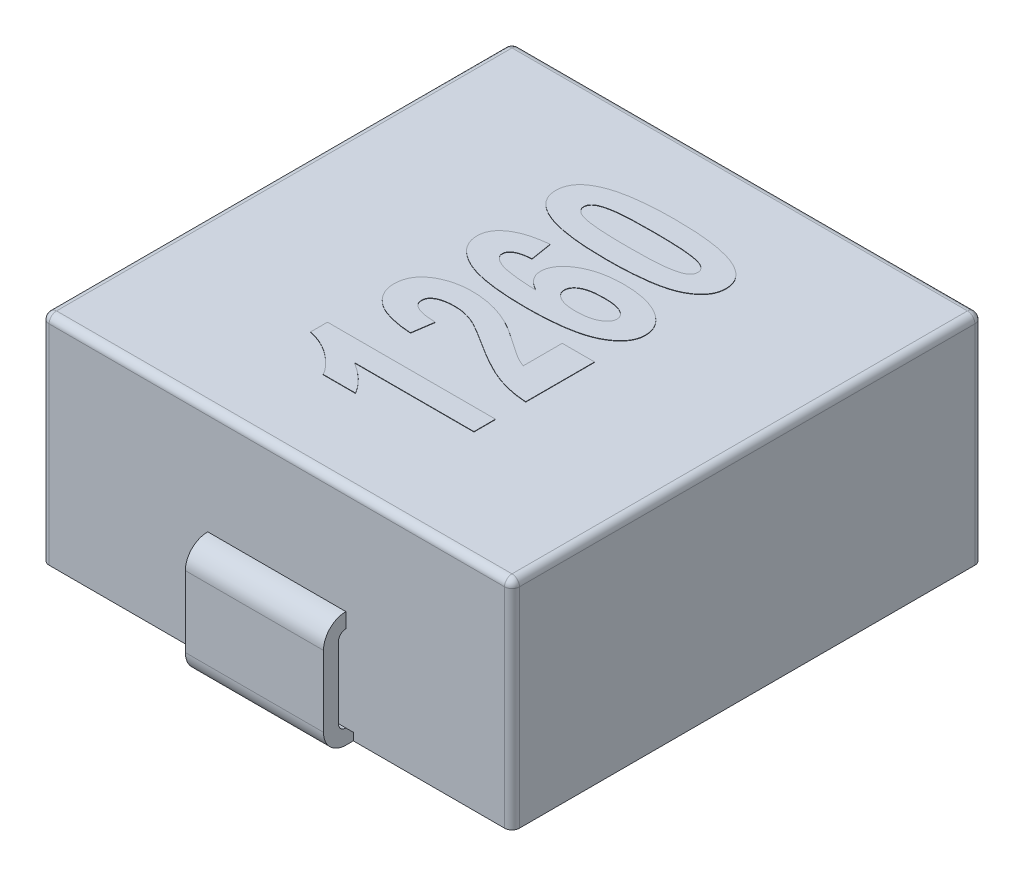
SolidWorks part; units mm, degrees
ref_plane "Спереди" through (0, 0, 0) normal (0, 0, 1) x (1, 0, 0)
ref_plane "Сверху" through (0, 0, 0) normal (0, 1, 0) x (1, 0, 0)
ref_plane "Справа" through (0, 0, 0) normal (1, 0, 0) x (0, 0, -1)
sketch "Эскиз1" plane through (0, 0, 0) normal (0, 1, 0) x (1, 0, 0)
  line L1 (-6.1, -6.3) -> (6.1, -6.3)
  line L2 (-6.3, -6.1) -> (-6.3, 6.1)
  line L3 (-6.1, 6.3) -> (6.1, 6.3)
  line L4 (6.3, -6.1) -> (6.3, 6.1)
  line L5 (-6.3, -6.3) -> (6.3, 6.3) construction
  line L6 (-6.3, 6.3) -> (6.3, -6.3) construction
  arc A0 (-6.1, -6.3) -> (-6.3, -6.1) centre (-6.1, -6.1) cw
  arc A1 (6.1, -6.3) -> (6.3, -6.1) centre (6.1, -6.1) ccw
  arc A2 (6.1, 6.3) -> (6.3, 6.1) centre (6.1, 6.1) cw
  arc A3 (-6.3, 6.1) -> (-6.1, 6.3) centre (-6.1, 6.1) cw
  point P0 (0, 0)
  dimension "D2" = 0.2
  dimension "D1" = 12.6
extrude "Бобышка-Вытянуть1" add sketch "Эскиз1" along normal blind 5.8
sketch "Эскиз2" plane through (0, 0, 0) normal (0, -1, 0) x (1, 0, 0)
  line L0 (-6.1, 6.3) -> (6.1, 6.3) construction
  line L1 (2.05, 6.3) -> (-2.05, 6.3)
  line L2 (2.05, 6.3) -> (2.05, 3.1)
  line L3 (2.05, 3.1) -> (-2.05, 3.1)
  line L4 (-2.05, 6.3) -> (-2.05, 3.1)
  line L5 (6.1, -6.3) -> (-6.1, -6.3) construction
  line L6 (2.05, -6.3) -> (-2.05, -6.3)
  line L7 (2.05, -6.3) -> (2.05, -3.1)
  line L8 (2.05, -3.1) -> (-2.05, -3.1)
  line L9 (-2.05, -6.3) -> (-2.05, -3.1)
  line L10 (-6.3, -6.1) -> (-6.3, 6.1) construction
  dimension "D1" = 4.25
  dimension "D2" = 4.1
  dimension "D3" = 3.2
extrude "Вырез-Вытянуть1" cut sketch "Эскиз2" against normal blind 0.2
sketch "Эскиз3" plane through (0, 0, 0) normal (1, 0, 0) x (0, 0, -1)
  line L0 (-6.3, 5.8) -> (-6.3, 0) construction
  line L1 (-6.9, 2.3) -> (-6.9, 0.4)
  line L2 (-6.3, -0.2) -> (-3.8, -0.2)
  line L3 (6.3, 5.8) -> (6.3, 0) construction
  line L4 (6.9, 2.3) -> (6.9, 0.4)
  line L5 (6.3, -0.2) -> (3.8, -0.2)
  line L6 (-6.3, 2.9) -> (6.3, 2.9) construction
  line L7 (-6.1, 0) -> (6.1, 0) construction
  arc A0 (-6.3, 2.9) -> (-6.9, 2.3) centre (-6.3, 2.3) ccw
  arc A1 (-6.9, 0.4) -> (-6.3, -0.2) centre (-6.3, 0.4) ccw
  arc A2 (6.3, 2.9) -> (6.9, 2.3) centre (6.3, 2.3) cw
  arc A3 (6.9, 0.4) -> (6.3, -0.2) centre (6.3, 0.4) cw
  dimension "D1" = 0.2
  dimension "D2" = 13.8
  dimension "D3" = 2.5
extrude "Вытянуть-Тонкостенный1" add sketch "Эскиз3" along normal mid plane 3.7 thin contours A0 L1 A1 L2 thin type one direction reverse wall 0.4
extrude "Вытянуть-Тонкостенный2" add sketch "Эскиз3<3>" along normal mid plane 3.7 thin contours A2 L4 A3 L5 thin type one direction wall 0.3
sketch "Эскиз3<3>" plane through (0, 0, 0) normal (1, 0, 0) x (0, 0, -1) same geometry as "Эскиз3"
fillet "Скругление1" radius 0.2 8 edges at (-6.2414, 5.8, 6.2414) (-6.3, 5.8, 0) (-6.2414, 5.8, -6.2414) (0, 5.8, -6.3) (6.2414, 5.8, -6.2414) (6.3, 5.8, 0) (6.2414, 5.8, 6.2414) (0, 5.8, 6.3)
sketch "Эскиз4" plane through (0, 5.8, 0) normal (0, 1, 0) x (1, 0, 0)
  line L0 (2.3, -4.3) -> (2.3, 6.3) construction
  line L1 (6.1, -6.3) -> (-6.1, -6.3) construction
  line L2 (6.3, 6.1) -> (6.3, -6.1) construction
  line L3 (-6.1, 6.3) -> (6.1, 6.3) construction
  text T0 "1260" font "Arial" height 4.5
  dimension "D1" = 2
  dimension "D2" = 4
extrude "Бобышка-Вытянуть2" add sketch "Эскиз4" along normal blind 0.01
equation "\"D1@Эскиз2\"=(\"D1@Эскиз1\"-\"D2@Эскиз2\")/2"
equation "\"D1@Вытянуть-Тонкостенный2\"=\"D1@Вытянуть-Тонкостенный1\""
